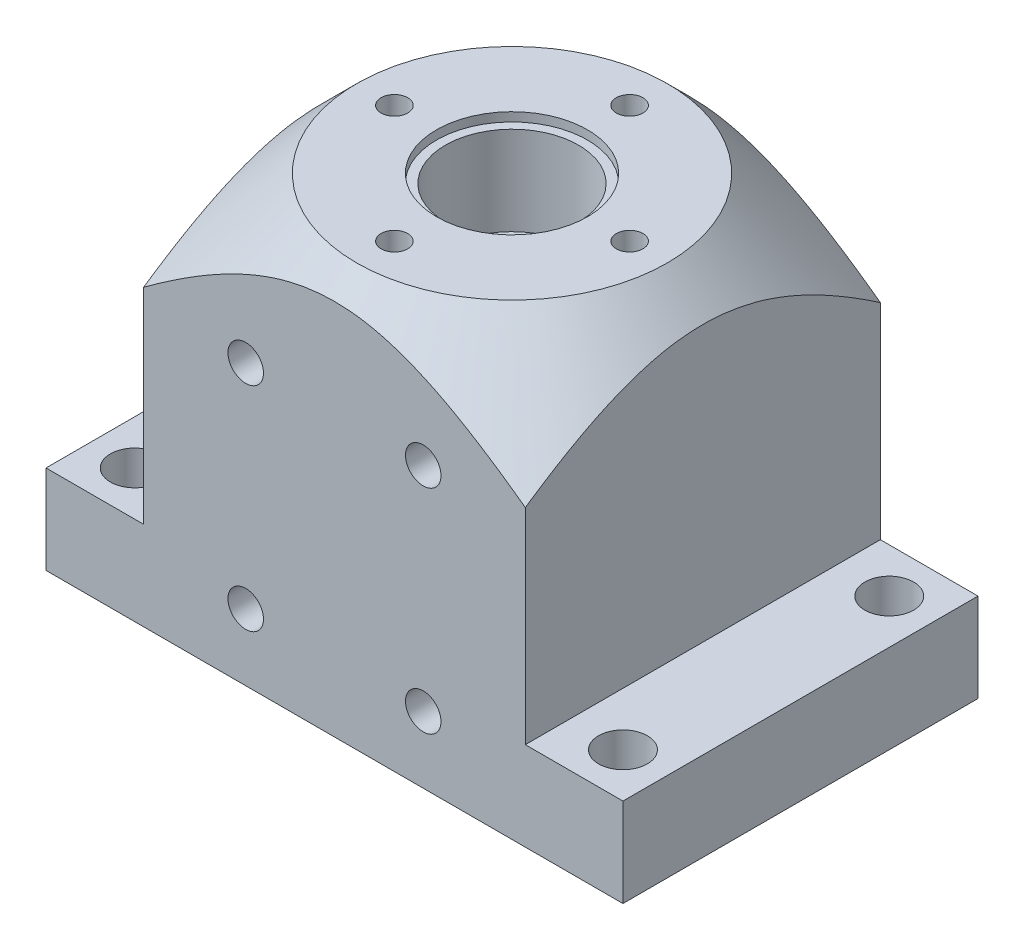
SolidWorks part; units mm, degrees
ref_plane "Alzado" through (0, 0, 0) normal (0, 0, 1) x (1, 0, 0)
ref_plane "Planta" through (0, 0, 0) normal (0, 1, 0) x (1, 0, 0)
ref_plane "Vista lateral" through (0, 0, 0) normal (1, 0, 0) x (0, 0, -1)
sketch "Croquis1" plane through (0, 0, 0) normal (0, 0, 1) x (1, 0, 0)
  line L0 (65, 0) -> (-65, 0)
  line L1 (-65, 0) -> (-65, 20)
  line L2 (-65, 20) -> (-43, 20)
  line L3 (-43, 20) -> (-43, 90)
  line L4 (-43, 90) -> (43, 90)
  line L5 (43, 90) -> (43, 20)
  line L6 (43, 20) -> (65, 20)
  line L7 (65, 20) -> (65, 0)
  point P6 (-43, 90)
  point P7 (43, 90)
  dimension "D1" = 65
  dimension "D2" = 65
  dimension "D3" = 20
  dimension "D4" = 20
  dimension "D5" = 43
  dimension "D6" = 43
  dimension "D7" = 90
extrude "Saliente-Extruir1" add sketch "Croquis1" along normal blind 40 and the other way blind 40
sketch "Croquis2" plane through (0, 90, 0) normal (0, 1, 0) x (1, 0, 0)
  circle A0 centre (0, 0) radius 17
  dimension "D1" = 34
extrude "Cortar-Extruir1" cut sketch "Croquis2" against normal blind 2
sketch "Croquis4" plane through (0, 0, 0) normal (0, 0, 1) x (1, 0, 0)
  line L0 (-35, 90) -> (-75.5525, 49.4475)
  line L1 (43, 90) -> (-43, 90) construction
  line L2 (-75.5525, 49.4475) -> (-75.5525, 90)
  line L3 (-75.5525, 90) -> (-35, 90)
  line L4 (0, 0) -> (0, -12.7157) construction
  dimension "D1" = 35
  dimension "D2" = 45
revolve "Cortar-Revolución2" cut sketch "Croquis4" angle 360 about L4
sketch "Croquis5" plane through (0, 88, 0) normal (0, 1, 0) x (1, 0, 0)
  circle A0 centre (0, 0) radius 13
  dimension "D1" = 26
extrude "Cortar-Extruir2" cut sketch "Croquis5" against normal up to next
sketch "Croquis6" plane through (0, 88, 0) normal (0, 1, 0) x (1, 0, 0)
  circle A0 centre (0, 0) radius 15
  dimension "D1" = 30
extrude "Cortar-Extruir3" cut sketch "Croquis6" against normal blind 20
sketch "Croquis7" plane through (0, 0, 0) normal (0, -1, 0) x (1, 0, 0)
  circle A0 centre (0, 0) radius 15
  dimension "D1" = 30
extrude "Cortar-Extruir4" cut sketch "Croquis7" against normal blind 20
sketch "Croquis8" plane through (0, 20, 0) normal (0, 1, 0) x (1, 0, 0)
  line L0 (-65, 40) -> (-65, -40) construction
  line L1 (-43, 40) -> (-65, 40) construction
  line L2 (-43, -40) -> (-65, -40) construction
  line L3 (65, -40) -> (43, -40) construction
  line L4 (65, 40) -> (65, -40) construction
  line L5 (65, 40) -> (43, 40) construction
  circle A0 centre (-55, 30) radius 5.5
  circle A1 centre (-55, -30) radius 5.5
  circle A2 centre (55, 30) radius 5.5
  circle A3 centre (55, -30) radius 5.5
  dimension "D1" = 11
  dimension "D2" = 11
  dimension "D3" = 11
  dimension "D4" = 11
  dimension "D5" = 10
  dimension "D6" = 10
  dimension "D7" = 10
  dimension "D8" = 10
  dimension "D9" = 10
  dimension "D10" = 10
  dimension "D11" = 10
  dimension "D12" = 10
extrude "Cortar-Extruir6" cut sketch "Croquis8" against normal up to next
sketch "Croquis9" plane through (0, 0, 40) normal (0, 0, 1) x (1, 0, 0)
  circle A0 centre (-20, 63) radius 4
  circle A1 centre (20, 63) radius 4
  circle A2 centre (20, 15) radius 4
  circle A3 centre (-20, 15) radius 4
  dimension "D1" = 8
  dimension "D2" = 8
  dimension "D3" = 8
  dimension "D4" = 8
extrude "Cortar-Extruir7" cut sketch "Croquis9" against normal blind 30
sketch "Croquis10" plane through (0, 90, 0) normal (0, 1, 0) x (1, 0, 0)
  circle A0 centre (0, 26.5) radius 3
  circle A1 centre (26.5, 0) radius 3
  circle A2 centre (0, -26.5) radius 3
  circle A3 centre (-26.5, 0) radius 3
  dimension "D1" = 6
  dimension "D2" = 6
  dimension "D3" = 6
  dimension "D4" = 6
extrude "Cortar-Extruir8" cut sketch "Croquis10" against normal blind 25
